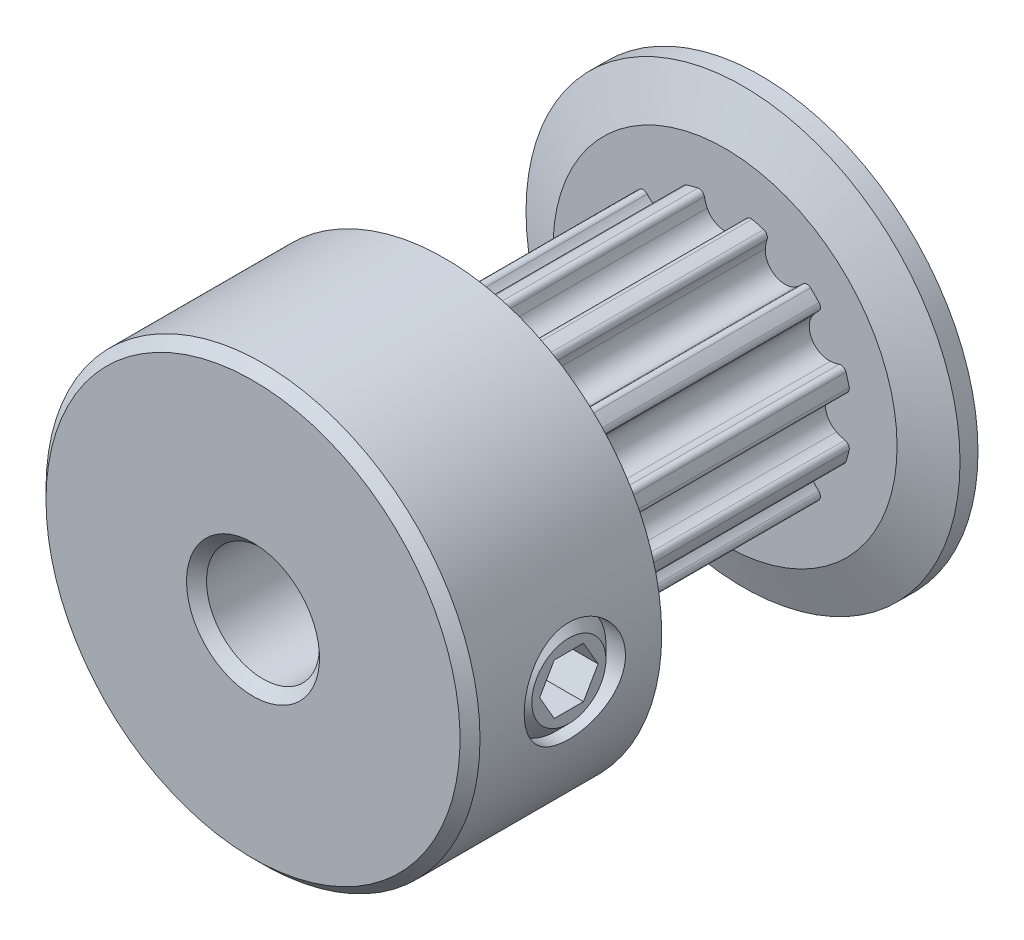
SolidWorks part; units mm, degrees
ref_plane "Front Plane" through (0, 0, 0) normal (0, 0, 1) x (1, 0, 0)
ref_plane "Top Plane" through (0, 0, 0) normal (0, 1, 0) x (1, 0, 0)
ref_plane "Right Plane" through (0, 0, 0) normal (1, 0, 0) x (0, 0, -1)
sketch "Sketch1" plane through (0, 0, 0) normal (0, 0, 1) x (1, 0, 0)
  line L1 (-1.6491, 2.8185) -> (1.6491, 2.8185) construction
  line L4 (0, 0) -> (0, 2.8185) construction
  line L5 (0, 2.8185) -> (0, 9.5178) construction
  line L6 (0, 3.8225) -> (1.9303, 3.2993) construction
  line L7 (1.9303, 3.2993) -> (2.4111, 3.018) construction
  line L8 (1.9303, 3.2993) -> (1.6491, 2.8185) construction
  line L9 (-1.9303, 3.2993) -> (-1.6491, 2.8185) construction
  line L10 (-1.8021, 3.08) -> (-3.5667, 6.096)
  line L11 (-3.5667, 6.096) -> (3.5667, 6.096)
  line L12 (3.5667, 6.096) -> (1.8021, 3.08)
  circle A0 centre (0, 0) radius 3.8225 construction
  circle A1 centre (0, 0) radius 6.096 construction
  circle A2 centre (0, 0) radius 3.5685 construction
  arc A3 (-0.4989, 3.1303) -> (0.4989, 3.1303) centre (0, 3.3735) ccw
  arc A4 (-0.4989, 3.1303) -> (-0.5801, 3.37) centre (0.4, 3.5685) cw
  arc A5 (-1.8021, 3.08) -> (-0.759, 3.4868) centre (0, 0) cw
  arc A6 (-0.5801, 3.37) -> (-0.759, 3.4868) centre (-0.7271, 3.3403) ccw
  arc A7 (1.8021, 3.08) -> (0.759, 3.4868) centre (0, 0) ccw
  arc A8 (0.5801, 3.37) -> (0.759, 3.4868) centre (0.7271, 3.3403) cw
  arc A9 (0.4989, 3.1303) -> (0.5801, 3.37) centre (-0.4, 3.5685) ccw
  point P6 (0, 20.9083)
  point P11 (0, 3.8225)
  point P13 (0, 6.096)
  point P14 (0, 3.5685)
  dimension "D1" = 11.3906
  dimension "D2" = 5.6953
sketch "Sketch2" plane through (0, 0, 0) normal (1, 0, 0) x (0, 0, -1)
  line L0 (-7.135, 1.5875) -> (7.135, 1.5875)
  line L1 (-7.135, 1.5875) -> (-7.135, 6.096)
  line L2 (-1.75, 6.096) -> (-7.135, 6.096)
  line L3 (-2.255, 1.5875) -> (-2.255, 6.096) construction
  line L4 (-2.255, 6.096) -> (-1.245, 6.096) construction
  line L5 (-1.245, 6.096) -> (-1.245, 3.5685) construction
  line L6 (-1.245, 3.5685) -> (6.125, 3.5685)
  line L7 (6.125, 3.5685) -> (6.125, 6.096) construction
  line L8 (6.125, 6.096) -> (7.135, 6.096) construction
  line L9 (7.135, 6.096) -> (7.135, 1.5875)
  line L10 (-7.135, 0) -> (7.135, 0) construction
  line L11 (6.63, 6.096) -> (6.125, 4.8323)
  line L12 (-1.245, 4.8323) -> (-1.75, 6.096)
  line L14 (-1.245, 4.8323) -> (-1.245, 3.5685)
  line L15 (6.125, 3.5685) -> (6.125, 4.8323)
  line L16 (6.63, 6.096) -> (7.135, 6.096)
  arc A0 (-1.245, 4.8323) -> (-1.75, 6.096) centre (-3.0788, 4.8323) ccw construction
  arc A1 (6.125, 4.8323) -> (6.63, 6.096) centre (7.9588, 4.8323) cw construction
  point P12 (-1.245, 4.8323)
  point P14 (-1.75, 6.096)
  point P20 (6.125, 4.8323)
  point P21 (6.63, 6.096)
  point P25 (6.125, 0)
  point P26 (-1.245, 0)
  dimension "OA" = 14.27
  dimension "Bore" = 3.175
  dimension "Outside Width" = 8.38
  dimension "Inside Width" = 7.37
revolve "Revolve1" add sketch "Sketch2" angle 360 mid plane about L10
sketch "Sketch3" plane through (0, 0, 0) normal (0, 0, 1) x (1, 0, 0)
  line L6 (3.5667, 6.096) -> (-3.5667, 6.096)
  line L7 (1.8021, 3.08) -> (3.5667, 6.096)
  line L8 (-3.5667, 6.096) -> (-1.8021, 3.08)
  line L9 (3.5667, 6.096) -> (-3.5667, 6.096)
  line L10 (1.8021, 3.08) -> (3.5667, 6.096)
  line L11 (-3.5667, 6.096) -> (-1.8021, 3.08)
  arc A8 (1.8021, 3.08) -> (0.759, 3.4868) centre (0, 0) ccw
  arc A9 (0.759, 3.4868) -> (0.5801, 3.37) centre (0.7271, 3.3403) ccw
  arc A10 (0.4989, 3.1303) -> (0.5801, 3.37) centre (-0.4, 3.5685) ccw
  arc A11 (-0.4989, 3.1303) -> (0.4989, 3.1303) centre (0, 3.3735) ccw
  arc A12 (-0.5801, 3.37) -> (-0.4989, 3.1303) centre (0.4, 3.5685) ccw
  arc A13 (-0.5801, 3.37) -> (-0.759, 3.4868) centre (-0.7271, 3.3403) ccw
  arc A14 (-0.759, 3.4868) -> (-1.8021, 3.08) centre (0, 0) ccw
  arc A15 (1.8021, 3.08) -> (0.759, 3.4868) centre (0, 0) ccw
  arc A16 (0.759, 3.4868) -> (0.5801, 3.37) centre (0.7271, 3.3403) ccw
  arc A17 (0.4989, 3.1303) -> (0.5801, 3.37) centre (-0.4, 3.5685) ccw
  arc A18 (-0.4989, 3.1303) -> (0.4989, 3.1303) centre (0, 3.3735) ccw
  arc A19 (-0.5801, 3.37) -> (-0.4989, 3.1303) centre (0.4, 3.5685) ccw
  arc A20 (-0.5801, 3.37) -> (-0.759, 3.4868) centre (-0.7271, 3.3403) ccw
  arc A21 (-0.759, 3.4868) -> (-1.8021, 3.08) centre (0, 0) ccw
  dimension "D1" = 0
extrude "Cut-Extrude1" cut sketch "Sketch3" against normal up to vertex (6.125 mm away) from vertex up to point (0, 3.5685, -6.125) starting at point (0, 3.5685, 1.245)
pattern_circular "CirPattern1" count 12 over 360 about axis through (0, 0, 7.135) along (0, 0, 1) of "Cut-Extrude1"
sketch "Sketch4" plane through (0, 0, 0) normal (1, 0, 0) x (0, -1, 0)
  line L0 (0, -1.245) -> (0, -7.135) construction
  line L1 (-1.5875, -7.135) -> (1.5875, -7.135) construction
  line L2 (4.8323, -1.245) -> (-4.8323, -1.245) construction
  circle A0 centre (0, -4.19) radius 1.4224
extrude "Cut-Extrude2" cut sketch "Sketch4" along normal through all
ref_plane "Plane1" through (0, 0, 4.19) normal (0, 0, 1) x (1, 0, 0)
sketch "Sketch5" plane through (0, 0, 4.19) normal (0, 0, 1) x (1, 0, 0)
  line L0 (0, 0) -> (0, 6.096) construction
  line L1 (1.5875, -1.0414) -> (1.5875, 0)
  line L2 (1.9685, -1.4224) -> (5.5467, -1.4224)
  line L3 (1.5875, 0) -> (6.096, 0) construction
  line L4 (1.5875, 0) -> (5.9277, 0)
  line L5 (5.9277, 0) -> (5.9277, -1.0414)
  line L6 (1.9685, -1.4224) -> (1.5875, -1.0414)
  line L7 (5.9277, -1.0414) -> (5.5467, -1.4224)
  circle A0 centre (0, 0) radius 6.096 construction
  circle A1 centre (0, 0) radius 1.5875 construction
  point P2 (1.5875, -1.4224)
  point P11 (5.9277, -1.4224)
revolve "Revolve2" add sketch "Sketch5" angle 360 mid plane about L4
sketch "Sketch6" plane through (5.9277, 5.3841, 0) normal (-1, 0, 0) x (0, -1, 0)
  line L1 (5.3841, 5.0112) -> (4.6729, 4.6006)
  line L2 (4.6729, 4.6006) -> (4.6729, 3.7794)
  line L3 (4.6729, 3.7794) -> (5.3841, 3.3688)
  line L4 (5.3841, 3.3688) -> (6.0953, 3.7794)
  line L5 (6.0953, 3.7794) -> (6.0953, 4.6006)
  line L6 (6.0953, 4.6006) -> (5.3841, 5.0112)
  circle A0 centre (5.3841, 4.19) radius 0.7112 construction
  dimension "D1" = 1.4224
extrude "Cut-Extrude3" cut sketch "Sketch6" along normal blind 1.0668
chamfer "Chamfer1" distance 0.2807 angle 45 2 edges at (1.5875, 0, 7.135) (6.096, 0, 7.135)
ref_axis "Center Axis 1" through (0, 0, -7.135) along (0, 0, 1)
ref_plane "Contact Plane 1" through (0, 0, 7.135) normal (0, 0, 1) x (1, 0, 0)
ref_plane "Contact Plane 2" through (0, 0, -7.135) normal (0, 0, -1) x (-1, 0, 0)
ref_axis "Axis1" through (0, 0, -7.135) along (0, 0, 1)
equation "\"D2@Sketch1\"= \"D1@Sketch1\" / 2"
equation "\"D1@Sketch6\" = \"Set Screw@Sketch4\" / 2"
equation "\"D1@Cut-Extrude3\" = \"D1@Sketch6\"*.75"
